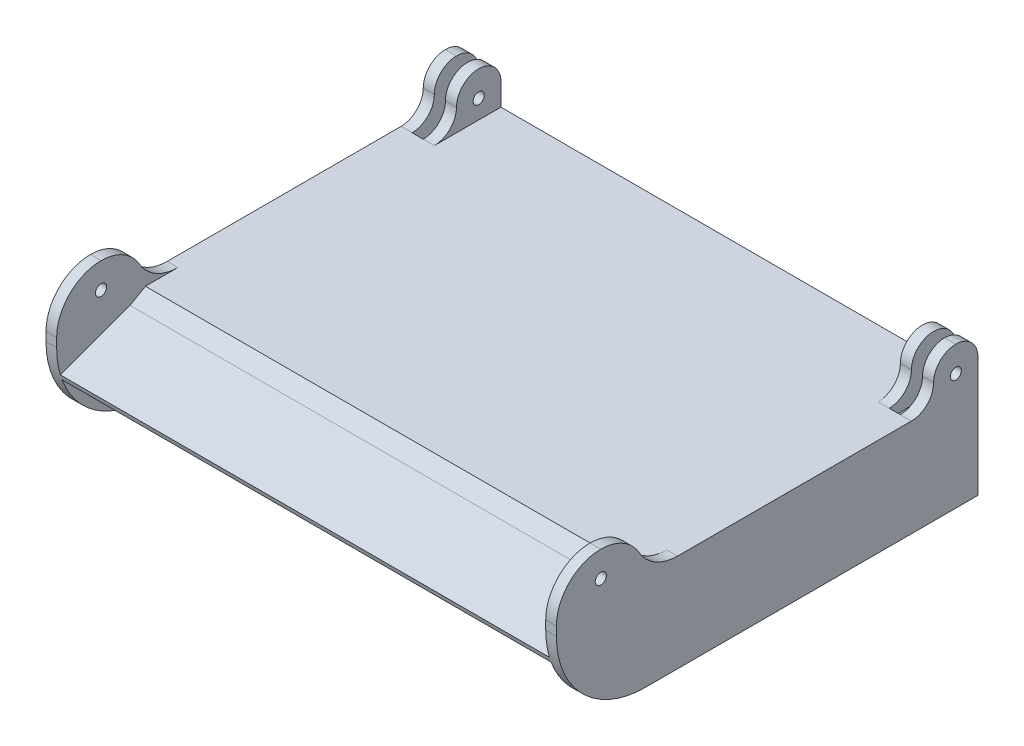
SolidWorks part; units mm, degrees
material "ABS"
ref_plane "Front Plane" through (0, 0, 0) normal (0, 0, 1) x (1, 0, 0)
ref_plane "Top Plane" through (0, 0, 0) normal (0, 1, 0) x (1, 0, 0)
ref_plane "Right Plane" through (0, 0, 0) normal (1, 0, 0) x (0, 0, -1)
sketch "Sketch1" plane through (0, 0, 0) normal (0, 1, 0) x (1, 0, 0)
  line L0 (15.748, -114.3) -> (130.302, -114.3)
  line L1 (0, 0) -> (146.05, 0)
  line L2 (0, 0) -> (0, -114.3)
  line L3 (0, -114.3) -> (3.048, -114.3)
  line L4 (146.05, 0) -> (146.05, -114.3)
  line L6 (3.048, -114.3) -> (3.048, -88.9)
  line L7 (3.048, -88.9) -> (15.748, -88.9)
  line L8 (15.748, -114.3) -> (15.748, -88.9)
  line L9 (73.025, 0) -> (73.025, -114.3) construction
  line L10 (143.002, -88.9) -> (130.302, -88.9)
  line L11 (143.002, -114.3) -> (143.002, -88.9)
  line L12 (130.302, -114.3) -> (130.302, -88.9)
  line L13 (143.002, -114.3) -> (146.05, -114.3)
  dimension "D1" = 114.3
  dimension "D2" = 146.05
  dimension "D3" = 3.048
  dimension "D4" = 12.7
  dimension "D5" = 25.4
extrude "Boss-Extrude1" add sketch "Sketch1" along normal blind 2.54
sketch "Sketch2" plane through (0, 2.54, 0) normal (0, 1, 0) x (1, 0, 0)
  line L0 (0, -114.3) -> (3.048, -114.3) construction
  line L1 (0, 0) -> (0, -114.3) construction
  line L2 (3.048, -114.3) -> (3.048, -88.9) construction
  line L3 (0, -114.3) -> (3.048, -114.3)
  line L4 (0, -88.9) -> (0, -114.3)
  line L5 (3.048, -114.3) -> (3.048, -88.9)
  line L6 (3.048, -88.9) -> (0, -88.9)
extrude "Boss-Extrude2" add sketch "Sketch2" along normal blind 12.7
ref_plane "Plane1" through (73.025, 0, 0) normal (1, 0, 0) x (0, 0, -1)
mirror "Mirror1" about plane through (73.025, 0, 0) normal (1, 0, 0) of "Boss-Extrude2"
fillet "Fillet5" radius 12.7 2 edges at (1.524, 15.24, 114.3) (1.524, 15.24, 88.9)
fillet "Fillet6" radius 12.7 1 edges at (1.524, 2.54, 88.9)
fillet "Fillet7" radius 12.7 2 edges at (144.526, 15.24, 114.3) (144.526, 15.24, 88.9)
fillet "Fillet8" radius 12.7 1 edges at (144.526, 2.54, 88.9)
sketch "Sketch3" plane through (146.05, 0, 0) normal (1, 0, 0) x (0, 0, -1)
  line L0 (-114.3, 0) -> (0, 0) construction
  circle A0 centre (-101.6, 7.9359) radius 1.5875
  dimension "D1" = 3.175
  dimension "D2" = 12.7
  dimension "D3" = 7.9359
extrude "Cut-Extrude1" cut sketch "Sketch3" against normal through all
sketch "Sketch4" plane through (146.05, 0, 0) normal (1, 0, 0) x (0, 0, -1)
  line L0 (-101.6, 7.9359) -> (0, 7.9359) construction
  line L1 (-79.603, 2.54) -> (0, 2.54) construction
  line L2 (-6.35, 2.54) -> (6.35, 2.54)
  line L3 (-6.35, 2.54) -> (-6.35, 15.24)
  line L4 (-6.35, 15.24) -> (6.35, 15.24)
  line L5 (6.35, 2.54) -> (6.35, 15.24)
  circle A0 centre (0, 7.9359) radius 1.5875
  dimension "D2" = 3.175
  dimension "D1" = 101.6
  dimension "D3" = 12.7
  dimension "D4" = 12.7
  dimension "D5" = 6.35
extrude "Boss-Extrude3" add sketch "Sketch4" against normal blind 3.175
sketch "Sketch5" plane through (0, 0, 0) normal (0, 0, -1) x (-1, 0, 0)
  line L5 (-146.05, 0) -> (0, 0)
  line L6 (0, 0) -> (0, 2.54)
  line L7 (0, 2.54) -> (-142.875, 2.54)
  line L8 (-142.875, 2.54) -> (-146.05, 2.54)
  line L9 (-146.05, 2.54) -> (-146.05, 0)
  line L10 (-146.05, 0) -> (0, 0)
  line L11 (0, 0) -> (0, 2.54)
  line L12 (0, 2.54) -> (-142.875, 2.54)
  line L13 (-142.875, 2.54) -> (-146.05, 2.54)
  line L14 (-146.05, 2.54) -> (-146.05, 0)
  dimension "D1" = 0
extrude "Boss-Extrude4" add sketch "Sketch5" along normal up to surface (6.35 mm away) up to face at (144.4625, 8.89, -6.35)
mirror "Mirror2" about plane through (73.025, 0, 0) normal (1, 0, 0) of "Boss-Extrude3"
fillet "Fillet10" radius 6.35 4 edges at (1.5875, 15.24, 6.35) (1.5875, 15.24, -6.35) (144.4625, 15.24, -6.35) (144.4625, 15.24, 6.35)
fillet "Fillet11" radius 6.35 2 edges at (1.5875, 2.54, 6.35) (144.4625, 2.54, 6.35)
sketch "Sketch6" plane through (0, 0, 0) normal (0, -1, 0) x (1, 0, 0)
  line L0 (142.875, 12.7) -> (142.875, -6.35) construction
  line L1 (142.875, 12.7) -> (142.875, -6.35)
  line L2 (142.875, 12.7) -> (139.7, 12.7)
  line L3 (139.7, 12.7) -> (139.7, -6.35)
  line L4 (146.05, -6.35) -> (0, -6.35) construction
  line L5 (142.875, -6.35) -> (139.7, -6.35)
  dimension "D1" = 3.175
extrude "Cut-Extrude2" cut sketch "Sketch6" against normal blind 3.175
mirror "Mirror3" about plane through (73.025, 0, 0) normal (1, 0, 0) of "Cut-Extrude2"
sketch "Sketch7" plane through (0, 0, 0) normal (0, -1, 0) x (1, 0, 0)
  line L0 (143.002, 114.3) -> (146.05, 114.3) construction
  line L1 (143.002, 88.9) -> (143.002, 114.3) construction
  line L2 (146.05, -6.35) -> (142.875, -6.35) construction
  line L3 (142.875, -6.35) -> (142.875, 12.7) construction
  line L4 (146.05, 114.3) -> (146.05, -6.35) construction
  line L5 (143.002, 114.3) -> (146.05, 114.3)
  line L6 (143.002, 88.9) -> (143.002, 114.3)
  line L7 (146.05, -6.35) -> (142.875, -6.35)
  line L8 (142.875, -6.35) -> (142.875, 12.7)
  line L9 (146.05, 114.3) -> (146.05, -6.35)
  line L10 (142.875, 12.7) -> (143.002, 88.9)
extrude "Boss-Extrude5" add sketch "Sketch7" along normal blind 25.4
mirror "Mirror4" about plane through (73.025, 0, 0) normal (1, 0, 0) of "Boss-Extrude5"
fillet "Fillet12" radius 25.4 2 edges at (1.524, -25.4, 114.3) (144.526, -25.4, 114.3)
sketch "Sketch8" plane through (0, 0, 0) normal (0, -1, 0) x (1, 0, 0)
  line L0 (139.7, 12.7) -> (139.7, -6.35) construction
  line L1 (139.7, -3.175) -> (6.35, -3.175)
  line L2 (139.7, -3.175) -> (139.7, -6.35)
  line L3 (139.7, -6.35) -> (6.35, -6.35)
  line L4 (6.35, -3.175) -> (6.35, -6.35)
  dimension "D1" = 3.175
extrude "Boss-Extrude6" add sketch "Sketch8" along normal blind 25.4
sketch "Sketch9" plane through (15.748, 0, 0) normal (-1, 0, 0) x (0, 0, 1)
  line L0 (114.3, 0) -> (114.3, -9.2448) construction
  line L1 (114.3, -9.2448) -> (88.9, 0)
  line L2 (88.9, 0) -> (93.2994, 0)
  line L3 (114.3, -9.2448) -> (114.3, -7.6436)
  line L4 (114.3, -7.6436) -> (93.2994, 0)
  line L7 (88.9, 2.54) -> (114.3, 2.54) construction
  line L8 (88.9, 0) -> (88.9, 2.54)
  line M7 (88.9, 0) -> (114.3, 0)
  dimension "D1" = 20
  dimension "D2" = 25.4
  dimension "D3" = 4.3994
  dimension "D4" = 21.0006
extrude "Boss-Extrude9" add sketch "Sketch9" against normal up to surface (114.554 mm away) contours L3 L4 L1 M7 region at (15.748, -4.2348, 102.6651) up to face at (130.302, 1.27, 101.6)
sketch "Sketch10" plane through (15.748, 0, 0) normal (-1, 0, 0) x (0, 0, 1)
  line L0 (93.2994, 0) -> (88.9, 2.54)
  line L1 (114.3, 2.54) -> (114.3, 0) construction
  line L2 (93.2994, 0) -> (114.3, 0) construction
  line L3 (88.9, 2.54) -> (114.3, 2.54) construction
  line L4 (114.3, 2.54) -> (114.3, 0)
  line L5 (93.2994, 0) -> (114.3, 0)
  line L6 (88.9, 2.54) -> (114.3, 2.54)
extrude "Cut-Extrude3" cut sketch "Sketch10" against normal up to next
sketch "Sketch11" plane through (15.748, 0, 0) normal (-1, 0, 0) x (0, 0, 1)
  line L4 (114.3, -7.6436) -> (93.2994, 0)
  line L5 (88.9, 2.54) -> (88.9, 0)
  line L6 (88.9, 0) -> (114.3, -9.2448)
  line L7 (114.3, -9.2448) -> (114.3, -7.6436)
  line L8 (114.3, -7.6436) -> (93.2994, 0)
  line L9 (88.9, 2.54) -> (88.9, 0)
  line L10 (88.9, 0) -> (114.3, -9.2448)
  line L11 (114.3, -9.2448) -> (114.3, -7.6436)
  line L13 (93.2994, 0) -> (88.9, 2.54)
  line L14 (93.2994, 0) -> (88.9, 2.54)
  dimension "D1" = 0
extrude "Boss-Extrude10" add sketch "Sketch11" along normal up to surface (12.7 mm away) up to face at (3.048, 7.9359, 103.1875)
sketch "Sketch12" plane through (130.302, 0, 0) normal (1, 0, 0) x (0, 0, -1)
  line L4 (-88.9, 0) -> (-88.9, 2.54)
  line L5 (-93.2994, 0) -> (-114.3, -7.6436)
  line L6 (-114.3, -7.6436) -> (-114.3, -9.2448)
  line L7 (-114.3, -9.2448) -> (-88.9, 0)
  line L8 (-88.9, 0) -> (-88.9, 2.54)
  line L9 (-93.2994, 0) -> (-114.3, -7.6436)
  line L10 (-114.3, -7.6436) -> (-114.3, -9.2448)
  line L11 (-114.3, -9.2448) -> (-88.9, 0)
  line L13 (-88.9, 2.54) -> (-93.2994, 0)
  line L14 (-88.9, 2.54) -> (-93.2994, 0)
  dimension "D1" = 0
extrude "Boss-Extrude11" add sketch "Sketch12" along normal up to surface (12.7 mm away) up to face at (143.002, 7.9359, 100.0125)
sketch "Sketch13" plane through (3.048, 0, 0) normal (-1, 0, 0) x (0, 0, 1)
  line L3 (114.3, -7.6436) -> (113.2409, -7.2581)
  line L4 (112.7682, -8.6873) -> (114.3, -9.2448)
  line L5 (114.3, -9.2448) -> (114.3, -7.6436)
  line L6 (114.3, -7.6436) -> (113.2409, -7.2581)
  line L7 (112.7682, -8.6873) -> (114.3, -9.2448)
  line L8 (114.3, -9.2448) -> (114.3, -7.6436)
  arc A1 (112.7682, -8.6873) -> (113.2409, -7.2581) centre (88.9, 0) ccw
  arc A2 (112.7682, -8.6873) -> (113.2409, -7.2581) centre (88.9, 0) ccw
  dimension "D1" = 0
extrude "Cut-Extrude4" cut sketch "Sketch13" against normal through all
fillet "Fillet15" radius 101.6 1 edges at (73.025, 0, 88.9)
ref_plane "Plane2" through (6.35, 0, 0) normal (-1, 0, 0) x (0, 0, 1)
sketch "Sketch14" plane through (6.35, 0, 0) normal (-1, 0, 0) x (0, 0, 1)
  line L0 (-6.35, 2.54) -> (12.7, 2.54) construction
  line L1 (-6.35, -25.4) -> (-6.35, 8.89) construction
  line L2 (-6.35, 2.54) -> (12.7, 2.54)
  line L3 (-6.35, 2.54) -> (-6.35, 8.89)
  arc A0 (6.35, 8.89) -> (0, 15.24) centre (0, 8.89) ccw construction
  arc A1 (0, 15.24) -> (-6.35, 8.89) centre (0, 8.89) ccw construction
  circle A2 centre (0, 7.9359) radius 1.5875 construction
  arc A3 (6.35, 8.89) -> (0, 15.24) centre (0, 8.89) ccw
  arc A4 (0, 15.24) -> (-6.35, 8.89) centre (0, 8.89) ccw
  circle A5 centre (0, 7.9359) radius 1.5875
  arc A6 (6.35, 8.89) -> (12.7, 2.54) centre (12.7, 8.89) ccw construction
  arc A7 (6.35, 8.89) -> (12.7, 2.54) centre (12.7, 8.89) ccw
extrude "Boss-Extrude12" add sketch "Sketch14" against normal blind 3.175
mirror "Mirror5" about plane through (73.025, 0, 0) normal (1, 0, 0) of "Boss-Extrude12"
